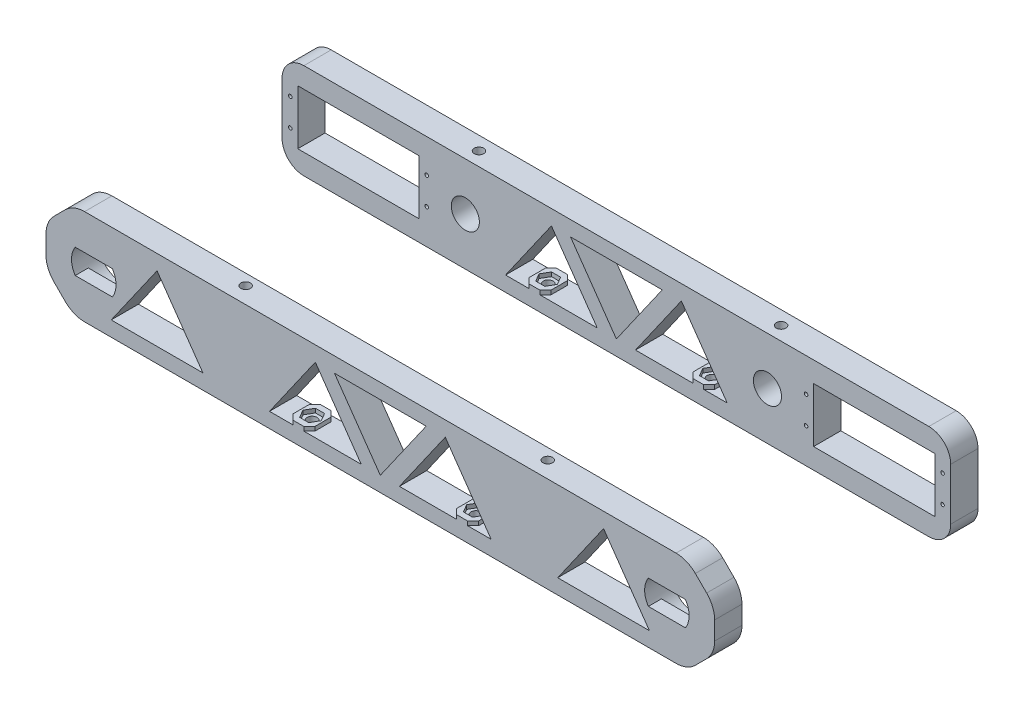
SolidWorks part; units mm, degrees
material "PLA 100% Infill"
ref_plane "Front Plane" through (0, 0, 0) normal (0, 0, 1) x (1, 0, 0)
ref_plane "Top Plane" through (0, 0, 0) normal (0, 1, 0) x (1, 0, 0)
ref_plane "Right Plane" through (0, 0, 0) normal (1, 0, 0) x (0, 0, -1)
sketch "Sketch1" plane through (0, 0, 0) normal (0, 0, 1) x (1, 0, 0)
  line L0 (-245, 17.5) -> (-154.7075, 17.5) construction
  line L1 (-245, 35) -> (0, 35)
  line L2 (-245, 35) -> (-245, 0)
  line L3 (-245, 0) -> (0, 0)
  line L4 (0, 35) -> (0, 0)
  line L5 (-122.5, 35) -> (-122.5, 17.5) construction
  line L6 (-163.11, 5.5) -> (-146.305, 29.5)
  line L7 (-146.305, 29.5) -> (-129.5, 5.5)
  line L8 (-129.5, 5.5) -> (-163.11, 5.5)
  line L9 (-139.305, 29.5) -> (-122.5, 5.5)
  line L10 (-122.5, 5.5) -> (-105.695, 29.5)
  line L11 (-105.695, 29.5) -> (-139.305, 29.5)
  line L12 (-146.305, 29.5) -> (-99.8936, 29.5) construction
  line L13 (-129.5, 5.5) -> (-123.2541, 5.5) construction
  line L14 (-74.6848, 5.5) -> (-74.6848, 29.5) construction
  line L21 (-122.5, 17.5) -> (-154.7075, 17.5) construction
  line L22 (-122.5, 17.5) -> (-90.2925, 17.5) construction
  line L23 (-98.695, 29.5) -> (-115.5, 5.5)
  line L24 (-81.89, 5.5) -> (-98.695, 29.5)
  line L25 (-115.5, 5.5) -> (-81.89, 5.5)
  line L27 (-122.5, 5.5) -> (-122.5, 0) construction
  circle A2 centre (-177.85, 17.5) radius 5.15
  circle A4 centre (-227.5, 17.5) radius 8.15
  circle A5 centre (-17.5, 17.5) radius 8.15
  circle A6 centre (-67.15, 17.5) radius 5.15
  point P12 (-183, 17.5)
  point P31 (-177.1567, 17.5)
  dimension "D2" = 35
  dimension "D3" = 16.3
  dimension "D4" = 10.3
  dimension "D5" = 245
  dimension "D6" = 49.65
  dimension "D7" = 24
  dimension "D9" = 7
  dimension "D10" = 110.7
  dimension "D8" = 70
extrude "Boss-Extrude1" add sketch "Sketch1" along normal blind 10 contours L4 A5 L1 L2 A4 L3 A2 A6 | A4 L2 | L4 A5 | A5 | A4 region at (-122.5, 32.5251, 0) region at (-227.5, 17.5, 0) region at (-17.5, 17.5, 0)
sketch "Sketch2" plane through (0, 0, 10) normal (0, 0, 1) x (1, 0, 0)
  circle A0 centre (-67.15, 17.5) radius 5.15 construction
  circle A1 centre (-67.15, 17.5) radius 5.15
  circle A2 centre (-177.85, 17.5) radius 5.15 construction
  circle A3 centre (-177.85, 17.5) radius 5.15
extrude "Boss-Extrude2" add sketch "Sketch2" against normal blind 2
ref_plane "Plane1" through (0, 0, -76.5) normal (0, 0, 1) x (1, 0, 0)
sketch "Sketch3" plane through (0, 0, -76.5) normal (0, 0, 1) x (1, 0, 0)
  line L0 (-245, 0) -> (0, 0) construction
  line L1 (-245, 35) -> (0, 35) construction
  line L2 (-245, 0) -> (0, 0)
  line L3 (-245, 35) -> (0, 35)
  line L4 (-194.75, 27.5) -> (-239.25, 27.5)
  line L5 (-194.75, 7.5) -> (-194.75, 27.5)
  line L6 (-239.25, 7.5) -> (-194.75, 7.5)
  line L7 (-239.25, 7.5) -> (-239.25, 27.5)
  line L8 (17.5, 17.5) -> (-243.5, 17.5) construction
  line L9 (-242, 22.7282) -> (-242, 12.7282) construction
  line L10 (-192, 22.7282) -> (-192, 12.7282) construction
  line L11 (-192, 12.7282) -> (-191.4311, 12.7282) construction
  line L12 (-122.5, 35) -> (-122.5, 0) construction
  line L13 (-50.25, 7.5) -> (-50.25, 27.5)
  line L14 (-5.75, 7.5) -> (-50.25, 7.5)
  line L15 (-5.75, 7.5) -> (-5.75, 27.5)
  line L16 (-50.25, 27.5) -> (-5.75, 27.5)
  line L18 (-98.695, 29.5) -> (-115.5, 5.5)
  line L21 (0, 35) -> (0, 0) construction
  line L22 (-245, 35) -> (-245, 0) construction
  line L23 (0, 35) -> (0, 0)
  line L24 (-245, 35) -> (-245, 0)
  line L31 (-122.5, 5.5) -> (-105.695, 29.5) construction
  line L32 (-105.695, 29.5) -> (-139.305, 29.5) construction
  line L33 (-139.305, 29.5) -> (-122.5, 5.5) construction
  line L34 (-129.5, 5.5) -> (-163.11, 5.5) construction
  line L35 (-146.305, 29.5) -> (-129.5, 5.5) construction
  line L36 (-163.11, 5.5) -> (-146.305, 29.5) construction
  line L43 (-122.5, 5.5) -> (-105.695, 29.5)
  line L44 (-105.695, 29.5) -> (-139.305, 29.5)
  line L45 (-139.305, 29.5) -> (-122.5, 5.5)
  line L46 (-129.5, 5.5) -> (-163.11, 5.5)
  line L47 (-146.305, 29.5) -> (-129.5, 5.5)
  line L48 (-163.11, 5.5) -> (-146.305, 29.5)
  line L49 (-81.89, 5.5) -> (-98.695, 29.5)
  line L50 (-115.5, 5.5) -> (-81.89, 5.5)
  circle A4 centre (-192, 12.7282) radius 0.65
  circle A5 centre (-192, 22.7282) radius 0.65
  circle A6 centre (-242, 12.7282) radius 0.65
  circle A7 centre (-242, 22.7282) radius 0.65
  circle A8 centre (-177.85, 17.5) radius 5.15 construction
  circle A9 centre (-177.85, 17.5) radius 5.15
  circle A10 centre (-3, 22.7282) radius 0.65
  circle A11 centre (-3, 12.7282) radius 0.65
  circle A12 centre (-53, 12.7282) radius 0.65
  circle A13 centre (-53, 22.7282) radius 0.65
  circle A14 centre (-67.15, 17.5) radius 5.15
  point P5 (-204.5, 17.5)
  point P21 (-194.75, 17.5)
  dimension "D10" = 1.3
  dimension "D1" = 2.75
  dimension "D2" = 20
  dimension "D3" = 44.5
  dimension "D4" = 2.75
  dimension "D5" = 10
  dimension "D6" = 5.2282
  dimension "D7" = 9.75
  dimension "D8" = 10
  dimension "D9" = 144.5
extrude "Boss-Extrude3" add sketch "Sketch3" against normal blind 10 separate body
sketch "Sketch4" plane through (0, 35, 0) normal (0, 1, 0) x (1, 0, 0)
  line L0 (-122.5, 86.5) -> (-122.5, -10) construction
  line L1 (0, 86.5) -> (-245, 86.5) construction
  line L2 (-245, -10) -> (0, -10) construction
  line L3 (-177.85, 86.5) -> (-177.85, -10) construction
  line L4 (-243.5, -4) -> (17.5, -4) construction
  line L5 (0, 86.5) -> (0, 76.5) construction
  line L6 (-245, 86.5) -> (-245, 76.5) construction
  line L7 (0, 81.5) -> (-245, 81.5) construction
  line L10 (-177.85, 39) -> (-122.5, 39) construction
  line L11 (-245, -10) -> (0, -10) construction
  circle A4 centre (-177.85, -4) radius 1.75
  circle A11 centre (-67.15, -4) radius 1.75
  circle A12 centre (-177.85, 81.5) radius 1.75
  circle A13 centre (-67.15, 81.5) radius 1.75
  point P10 (0, 0)
  point P13 (0, 0)
  point P14 (-177.85, 81.5)
  point P19 (-177.85, 81.5)
  point P20 (0, 0)
  point P23 (-177.85, 82)
  point P24 (0, 81.5)
  point P27 (-245, 81.5)
  point P32 (-177.85, 81.5)
  dimension "D1" = 0
  dimension "D4" = 3.5
  dimension "D2" = 55.35
  dimension "D5" = 6
  dimension "D6" = 43
extrude "Cut-Extrude1" cut sketch "Sketch4" against normal blind 10
chamfer "Chamfer1" distance 10 angle 45 4 edges at (0, 35, 5) (0, 0, 5) (-245, 0, 5) (-245, 35, 5)
fillet "Fillet1" radius 8 4 edges at (0, 0, -81.5) (0, 35, -81.5) (-245, 0, -81.5) (-245, 35, -81.5)
sketch "Sketch6" plane through (0, 0, 10) normal (0, 0, 1) x (1, 0, 0)
  line L0 (-122.5, 5.5) -> (-105.695, 29.5) construction
  line L1 (-187.5, 5.5) -> (-221.11, 5.5)
  line L2 (-139.305, 29.5) -> (-122.5, 5.5) construction
  line L3 (-221.11, 5.5) -> (-204.305, 29.5)
  line L4 (-146.305, 29.5) -> (-129.5, 5.5) construction
  line L5 (-163.11, 5.5) -> (-146.305, 29.5) construction
  line L6 (-122.5, 5.5) -> (-105.695, 29.5)
  line L7 (-105.695, 29.5) -> (-139.305, 29.5)
  line L8 (-139.305, 29.5) -> (-122.5, 5.5)
  line L9 (-129.5, 5.5) -> (-163.11, 5.5)
  line L10 (-146.305, 29.5) -> (-129.5, 5.5)
  line L11 (-163.11, 5.5) -> (-146.305, 29.5)
  line L12 (-204.305, 29.5) -> (-187.5, 5.5)
  line L13 (-115.5, 5.5) -> (-81.89, 5.5) construction
  line L14 (-81.89, 5.5) -> (-98.695, 29.5) construction
  line L15 (-98.695, 29.5) -> (-115.5, 5.5) construction
  line L16 (-115.5, 5.5) -> (-81.89, 5.5)
  line L17 (-81.89, 5.5) -> (-98.695, 29.5)
  line L18 (-98.695, 29.5) -> (-115.5, 5.5)
  line L19 (-57.5, 5.5) -> (-23.89, 5.5)
  line L20 (-23.89, 5.5) -> (-40.695, 29.5)
  line L21 (-40.695, 29.5) -> (-57.5, 5.5)
  dimension "D3" = 58
  dimension "D4" = 58
  dimension "D1" = 2
  dimension "D2" = 2
extrude "Cut-Extrude3" cut sketch "Sketch6" against normal blind 10 contours L20 L21 L19 | L1 L3 L12 region at (-40.695, 13.5, 10)
sketch "Sketch7" plane through (0, 5.5, 0) normal (0, 1, 0) x (1, 0, 0)
  line L0 (-163.11, 81.5) -> (-81.89, 81.5) construction
  line L1 (-163.11, 86.5) -> (-163.11, 76.5) construction
  line L2 (-81.89, 86.5) -> (-81.89, 76.5) construction
  line L3 (-227.4452, 0) -> (-227.4452, 76.5) construction
  line L4 (-235, 0) -> (-10, 0) construction
  line L5 (-239.25, 76.5) -> (-194.75, 76.5) construction
  line L6 (-227.4452, 38.25) -> (0, 38.25) construction
  line L7 (0, 38.25) -> (0, 0) construction
  line L8 (-122.5, 81.5) -> (-122.5, -5) construction
  line L9 (-122.5, -10) -> (-122.5, 0) construction
  line L10 (-155.8486, 81.5) -> (-154.1743, 84.4)
  line L11 (-154.1743, 84.4) -> (-150.8257, 84.4)
  line L12 (-150.8257, 84.4) -> (-149.1514, 81.5)
  line L13 (-149.1514, 81.5) -> (-150.8257, 78.6)
  line L14 (-150.8257, 78.6) -> (-154.1743, 78.6)
  line L15 (-154.1743, 78.6) -> (-155.8486, 81.5)
  line L16 (-150.8257, 84.4) -> (-154.1743, 78.6) construction
  line L17 (-90.8257, 78.6) -> (-89.1514, 81.5)
  line L18 (-94.1743, 78.6) -> (-90.8257, 78.6)
  line L19 (-95.8486, 81.5) -> (-94.1743, 78.6)
  line L20 (-94.1743, 84.4) -> (-95.8486, 81.5)
  line L21 (-90.8257, 84.4) -> (-94.1743, 84.4)
  line L22 (-89.1514, 81.5) -> (-90.8257, 84.4)
  line L23 (-94.1743, -2.1) -> (-90.8257, -2.1)
  line L24 (-95.8486, -5) -> (-94.1743, -2.1)
  line L25 (-94.1743, -7.9) -> (-95.8486, -5)
  line L26 (-90.8257, -7.9) -> (-94.1743, -7.9)
  line L27 (-89.1514, -5) -> (-90.8257, -7.9)
  line L28 (-90.8257, -2.1) -> (-89.1514, -5)
  line L29 (-150.8257, -2.1) -> (-154.1743, -2.1)
  line L30 (-149.1514, -5) -> (-150.8257, -2.1)
  line L31 (-150.8257, -7.9) -> (-149.1514, -5)
  line L32 (-154.1743, -7.9) -> (-150.8257, -7.9)
  line L33 (-155.8486, -5) -> (-154.1743, -7.9)
  line L34 (-154.1743, -2.1) -> (-155.8486, -5)
  line L35 (-163.11, 86.5) -> (-129.5, 86.5) construction
  line L36 (-156.5, 86.5) -> (-148.5, 86.5)
  line L37 (-156.5, 86.5) -> (-156.5, 76.5)
  line L38 (-156.5, 76.5) -> (-148.5, 76.5)
  line L39 (-148.5, 86.5) -> (-148.5, 76.5)
  line L40 (-163.11, 76.5) -> (-129.5, 76.5) construction
  line L41 (-156.5, 86.5) -> (-148.5, 76.5) construction
  line L42 (-88.5, 76.5) -> (-96.5, 76.5)
  line L43 (-96.5, 86.5) -> (-96.5, 76.5)
  line L44 (-88.5, 86.5) -> (-96.5, 86.5)
  line L45 (-88.5, 86.5) -> (-88.5, 76.5)
  line L46 (-88.5, -10) -> (-88.5, 0)
  line L47 (-88.5, -10) -> (-96.5, -10)
  line L48 (-96.5, -10) -> (-96.5, 0)
  line L49 (-88.5, 0) -> (-96.5, 0)
  line L50 (-156.5, 0) -> (-148.5, 0)
  line L51 (-148.5, -10) -> (-148.5, 0)
  line L52 (-156.5, -10) -> (-148.5, -10)
  line L53 (-156.5, -10) -> (-156.5, 0)
  circle A2 centre (-152.5, 81.5) radius 1.8
  circle A3 centre (-92.5, 81.5) radius 1.8
  circle A4 centre (-92.5, -5) radius 1.8
  circle A5 centre (-152.5, -5) radius 1.8
  line M19 (-81.89, 0) -> (-115.5, 0)
  line M21 (-115.5, -10) -> (-81.89, -10)
  dimension "D1" = 30
  dimension "D2" = 3.6
  dimension "D3" = 5.8
  dimension "D4" = 8
extrude "Cut-Extrude4" cut sketch "Sketch7" against normal blind 10 contours A5 | A4 | A2 | A3 region at (-152.5, 5.5, -81.5) region at (-92.5, 5.5, -81.5) region at (-92.5, 5.5, 5) region at (-152.5, 5.5, 5)
extrude "Boss-Extrude4" add sketch "Sketch7<3>" along normal blind 1.5 contours L53 L52 L51 L50 L34 L29 L30 L31 L32 L33 | L48 L46 L23 L28 L27 L26 L25 L24 M21 M19 | L45 L44 L43 L42 L22 L17 L18 L19 L20 L21 | L39 L36 L37 L38 L14 L15 L10 L11 L12 L13 region at (-152.5, 5.5, -86.3719) region at (-92.5, 5.5, -76.6281) region at (-92.5, 5.5, 9.8719) region at (-152.5, 5.5, 0.1281)
sketch "Sketch7<3>" plane through (0, 5.5, 0) normal (0, 1, 0) x (1, 0, 0) same geometry as "Sketch7"
chamfer "Chamfer2" distance 2 angle 45 8 edges at (-96.5, 6.25, -76.5) (-88.5, 6.25, -76.5) (-88.5, 6.25, -86.5) (-96.5, 6.25, -86.5) (-148.5, 6.25, -86.5) (-156.5, 6.25, -86.5) (-148.5, 6.25, -76.5) (-156.5, 6.25, -76.5)
chamfer "Chamfer3" distance 2 angle 45 8 edges at (-88.5, 6.25, 0) (-88.5, 6.25, 10) (-96.5, 6.25, 10) (-96.5, 6.25, 0) (-148.5, 6.25, 0) (-148.5, 6.25, 10) (-156.5, 6.25, 10) (-156.5, 6.25, 0)
fillet "Fillet2" radius 10 8 edges at (-10, 35, 5) (-10, 0, 5) (0, 10, 5) (0, 25, 5) (-235, 0, 5) (-245, 10, 5) (-245, 25, 5) (-235, 35, 5)
extrude "Cut-Extrude5" cut sketch "Sketch1<3>" along normal blind 5.2 contours A4 | A5 region at (-227.5, 17.5, 0) region at (-17.5, 17.5, 0)
sketch "Sketch1<3>" plane through (0, 0, 0) normal (0, 0, 1) x (1, 0, 0) same geometry as "Sketch1"
sketch "Sketch8" plane through (0, 0, 0) normal (0, 0, -1) x (-1, 0, 0)
  line L0 (10.705, 22) -> (24.295, 22)
  line L1 (10.705, 13) -> (24.295, 13)
  line L2 (220.705, 22) -> (234.295, 22)
  line L3 (220.705, 13) -> (234.295, 13)
  circle A3 centre (227.5, 17.5) radius 8.15 construction
  arc A4 (220.705, 22) -> (220.705, 13) centre (227.5, 17.5) ccw
  circle A5 centre (17.5, 17.5) radius 8.15 construction
  arc A6 (10.705, 22) -> (10.705, 13) centre (17.5, 17.5) ccw
  arc A7 (24.295, 13) -> (24.295, 22) centre (17.5, 17.5) ccw
  arc A8 (234.295, 13) -> (234.295, 22) centre (227.5, 17.5) ccw
  point P14 (233.936, 22.5)
  point P15 (0, 0)
  point P16 (0, 0)
  dimension "D1" = 4.5
  dimension "D2" = 4.5
extrude "Cut-Extrude6" cut sketch "Sketch8" against normal through all
sketch "Sketch9" plane through (0, 25, 0) normal (0, 1, 0) x (1, 0, 0)
  line L0 (-67.15, 81.5) -> (-67.15, -4) construction
  line L1 (-67.15, -4) -> (-177.85, -4) construction
  line L2 (-122.5, -4) -> (-122.5, 76.5) construction
  line L3 (-67.15, 38.75) -> (-122.5, 38.75) construction
  circle A0 centre (-177.85, -4) radius 0.65
  circle A2 centre (-67.15, -4) radius 0.65
  circle A3 centre (-67.15, 81.5) radius 0.65
  circle A4 centre (-177.85, 81.5) radius 0.65
  dimension "D1" = 1.3
extrude "Cut-Extrude7" cut sketch "Sketch9" against normal blind 5.2
